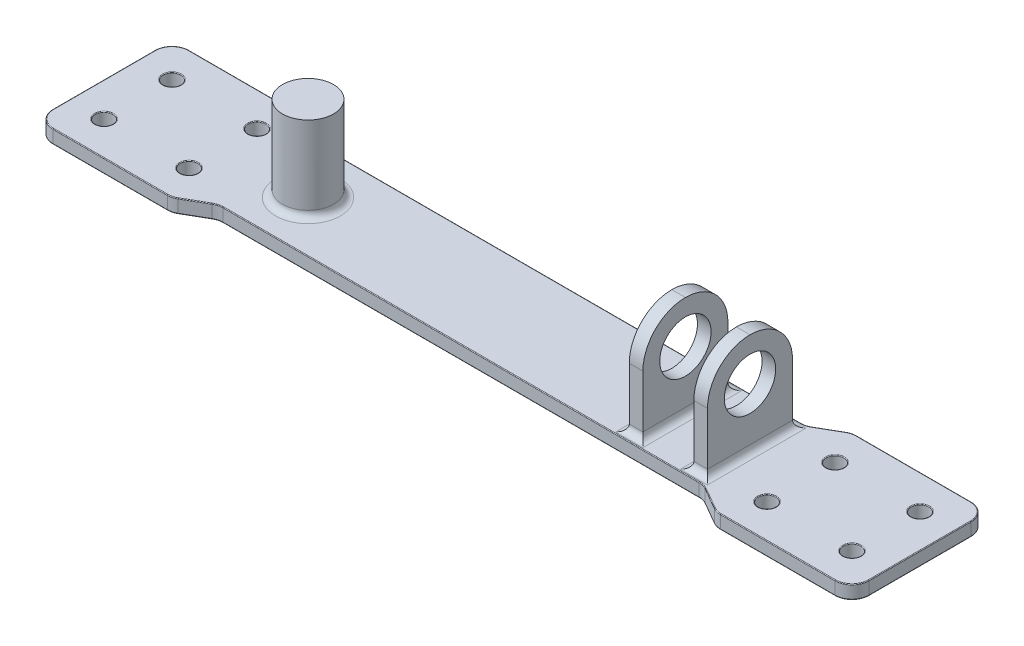
SolidWorks part; units mm, degrees
ref_plane "Front Plane" through (0, 0, 0) normal (0, 0, 1) x (1, 0, 0)
ref_plane "Top Plane" through (0, 0, 0) normal (0, 1, 0) x (1, 0, 0)
ref_plane "Right Plane" through (0, 0, 0) normal (1, 0, 0) x (0, 0, -1)
sketch "Sketch1" plane through (0, 0, 0) normal (0, 1, 0) x (1, 0, 0)
  line L0 (-120, 0) -> (120, 0) construction
  line L1 (-120, -15) -> (-120, 15)
  line L2 (-115, 20) -> (-81.3397, 20)
  line L3 (-78.8397, 19.3301) -> (-72.5, 15.6699)
  line L4 (-70, 15) -> (70, 15)
  line L5 (72.5, 15.6699) -> (78.8397, 19.3301)
  line L6 (81.3397, 20) -> (115, 20)
  line L7 (120, 15) -> (120, -15)
  line L8 (81.3397, -20) -> (115, -20)
  line L9 (72.5, -15.6699) -> (78.8397, -19.3301)
  line L10 (-70, -15) -> (70, -15)
  line L11 (-78.8397, -19.3301) -> (-72.5, -15.6699)
  line L12 (-115, -20) -> (-81.3397, -20)
  line L13 (-110, 10) -> (-85, 10) construction
  line L14 (-110, 10) -> (-110, -10) construction
  line L15 (0, 0) -> (0, 15) construction
  arc A0 (115, 20) -> (120, 15) centre (115, 15) cw
  arc A1 (115, -20) -> (120, -15) centre (115, -15) ccw
  arc A2 (-115, -20) -> (-120, -15) centre (-115, -15) cw
  arc A3 (-120, 15) -> (-115, 20) centre (-115, 15) cw
  arc A4 (-72.5, 15.6699) -> (-70, 15) centre (-70, 20) ccw
  arc A5 (-70, -15) -> (-72.5, -15.6699) centre (-70, -20) ccw
  arc A6 (72.5, -15.6699) -> (70, -15) centre (70, -20) ccw
  arc A7 (70, 15) -> (72.5, 15.6699) centre (70, 20) ccw
  arc A8 (78.8397, 19.3301) -> (81.3397, 20) centre (81.3397, 15) cw
  arc A9 (81.3397, -20) -> (78.8397, -19.3301) centre (81.3397, -15) cw
  arc A10 (-78.8397, -19.3301) -> (-81.3397, -20) centre (-81.3397, -15) cw
  arc A11 (-81.3397, 20) -> (-78.8397, 19.3301) centre (-81.3397, 15) cw
  circle A12 centre (-110, 10) radius 2.6
  circle A13 centre (-85, 10) radius 2.6
  circle A14 centre (-85, -10) radius 2.6
  circle A15 centre (-110, -10) radius 2.6
  circle A16 centre (85, -10) radius 2.6
  circle A17 centre (110, -10) radius 2.6
  circle A18 centre (85, 10) radius 2.6
  circle A19 centre (110, 10) radius 2.6
  point P1 (0, 15)
  point P18 (120, 20)
  point P21 (120, -20)
  point P24 (-120, -20)
  point P27 (-120, 20)
  point P30 (-71.3397, 15)
  point P33 (-71.3397, -15)
  point P36 (71.3397, -15)
  point P39 (71.3397, 15)
  point P42 (80, 20)
  point P45 (80, -20)
  point P48 (-80, -20)
  point P51 (-80, 20)
  dimension "D6" = 5
  dimension "D7" = 5
  dimension "D8" = 5.2
  dimension "D1" = 240
  dimension "D2" = 40
  dimension "D3" = 15
  dimension "D4" = 5
  dimension "D5" = 150
  dimension "D9" = 10
  dimension "D10" = 10
  dimension "D13" = 90
  dimension "D14" = 25
  dimension "D15" = 20
  dimension "D11" = 2
  dimension "D12" = 2
extrude "Boss-Extrude1" add sketch "Sketch1" along normal blind 4
sketch "Sketch2" plane through (0, 4, 0) normal (0, 1, 0) x (1, 0, 0)
  line L1 (47, 12.5) -> (51, 12.5)
  line L2 (47, 12.5) -> (47, -12.5)
  line L3 (47, -12.5) -> (51, -12.5)
  line L4 (51, 12.5) -> (51, -12.5)
  line L5 (47, 12.5) -> (51, -12.5) construction
  line L6 (47, -12.5) -> (51, 12.5) construction
  line L7 (66, 12.5) -> (70, 12.5)
  line L8 (66, 12.5) -> (66, -12.5)
  line L9 (66, -12.5) -> (70, -12.5)
  line L10 (70, 12.5) -> (70, -12.5)
  line L11 (66, 12.5) -> (70, -12.5) construction
  line L12 (66, -12.5) -> (70, 12.5) construction
  line L13 (120, -15) -> (120, 15) construction
  point P0 (49, 0)
  point P5 (68, 0)
  point P10 (0, 0)
  point P12 (32.0189, -8.5932)
  point P13 (49.2647, -12.5)
  point P18 (100, 10.7562)
  dimension "D1" = 4
  dimension "D2" = 25
  dimension "D3" = 15
  dimension "D4" = 50
extrude "Boss-Extrude2" add sketch "Sketch2" along normal blind 30
fillet "Fillet2" radius 12.5 4 edges at (49, 34, 12.5) (68, 34, 12.5) (68, 34, -12.5) (49, 34, -12.5)
sketch "Sketch4" plane through (47, 0, 0) normal (-1, 0, 0) x (0, 0, 1)
  circle A0 centre (0, 21.5) radius 7.55
  dimension "D1" = 15.1
extrude "Cut-Extrude1" cut sketch "Sketch4" against normal blind 30
sketch "Sketch5" plane through (0, 4, 0) normal (0, 1, 0) x (1, 0, 0)
  circle A0 centre (-60, 0) radius 7.5
  point P2 (0, 0)
  dimension "D1" = 15
  dimension "D2" = 60
extrude "Boss-Extrude3" add sketch "Sketch5" along normal blind 25
fillet "Fillet3" radius 2 9 edges at (49, 4, 12.5) (68, 4, 12.5) (68, 4, -12.5) (49, 4, -12.5) (47, 4, 0) (70, 4, 0) (51, 4, 0) (66, 4, 0) (-60, 4, -7.5)
fillet "Fillet6" radius 0.2 64 edges at (110, 0, -12.6) (110, 0, 7.4) (-110, 0, 12.6) (-85, 0, -7.4) (98.1699, 0, -20) (80.0457, 0, -19.8296) (75.6699, 0, -17.5) (71.2941, 0, -15.1704) (0, 0, -15) (-71.2941, 0, -15.1704) (-75.6699, 0, -17.5) (-80.0457, 0, -19.8296) (-98.1699, 0, -20) (-118.5355, 0, -18.5355) (-120, 0, 0) (-118.5355, 0, 18.5355) (-98.1699, 0, 20) (-80.0457, 0, 19.8296) (-75.6699, 0, 17.5) (-71.2941, 0, 15.1704) (0, 0, 15) (71.2941, 0, 15.1704) (75.6699, 0, 17.5) (80.0457, 0, 19.8296) (98.1699, 0, 20) (118.5355, 0, 18.5355) (120, 0, 0) (118.5355, 0, -18.5355) (-110, 0, -7.4) (-85, 0, 12.6) (85, 0, 7.4) (85, 0, -12.6) (110, 4, -12.6) (85, 4, -12.6) (110, 4, 7.4) (85, 4, 7.4) (-110, 4, 12.6) (-85, 4, 12.6) (-85, 4, -7.4) (-110, 4, -7.4) (120, 4, 0) (118.5355, 4, 18.5355) (98.1699, 4, 20) (80.0457, 4, 19.8296) (75.6699, 4, 17.5) (71.2941, 4, 15.1704) (0, 4, 15) (-71.2941, 4, 15.1704) (-75.6699, 4, 17.5) (-80.0457, 4, 19.8296) (-98.1699, 4, 20) (-118.5355, 4, 18.5355) (-120, 4, 0) (-118.5355, 4, -18.5355) (-98.1699, 4, -20) (-80.0457, 4, -19.8296) (-75.6699, 4, -17.5) (-71.2941, 4, -15.1704) (0, 4, -15) (71.2941, 4, -15.1704) (75.6699, 4, -17.5) (80.0457, 4, -19.8296) (98.1699, 4, -20) (118.5355, 4, -18.5355)
